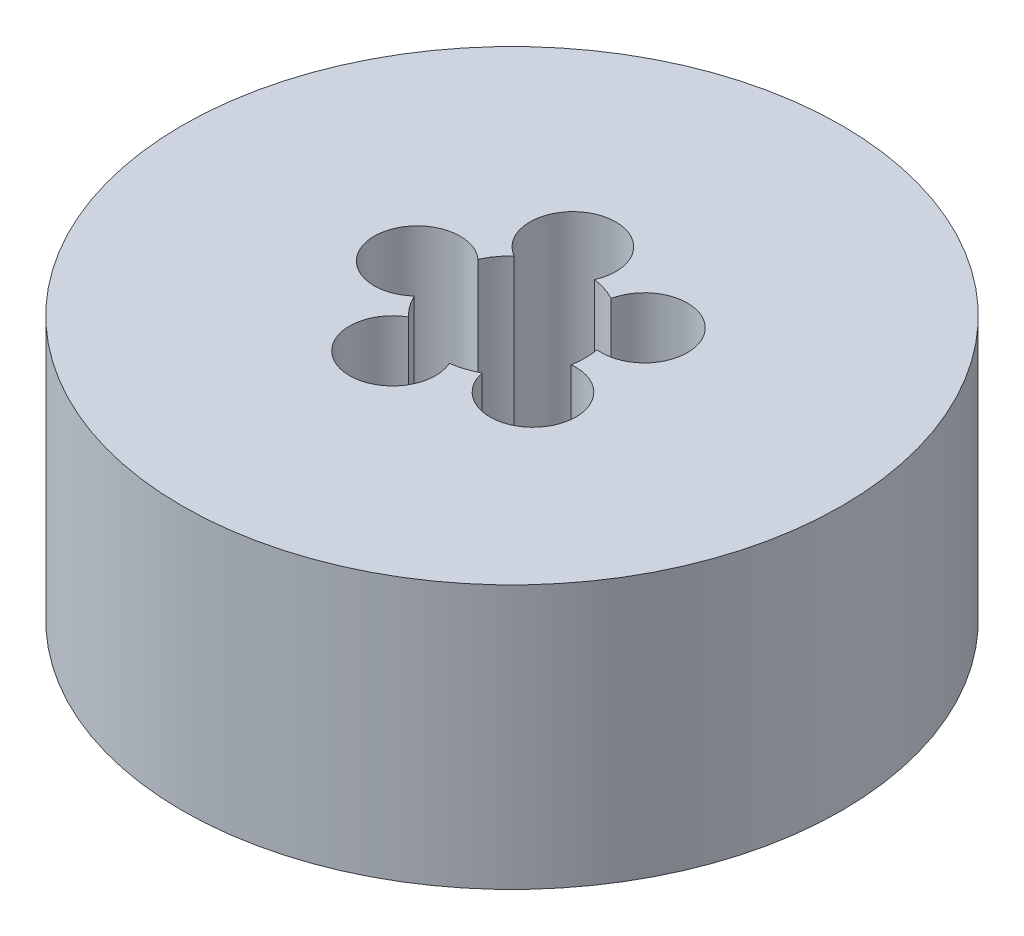
SolidWorks part; units mm, degrees
ref_plane "Front Plane" through (0, 0, 0) normal (0, 0, 1) x (1, 0, 0)
ref_plane "Top Plane" through (0, 0, 0) normal (0, 1, 0) x (1, 0, 0)
ref_plane "Right Plane" through (0, 0, 0) normal (1, 0, 0) x (0, 0, -1)
sketch "Sketch1" plane through (0, 0, 0) normal (0, 1, 0) x (1, 0, 0)
  circle A0 centre (0, 0) radius 22.5
  dimension "FLANGE_OD" = 45
extrude "Boss-Extrude1" add sketch "Sketch1" along normal blind 18
sketch "Sketch2" plane through (0, 0, 0) normal (0, 1, 0) x (1, 0, 0)
  circle A0 centre (0, 0) radius 5
  dimension "BORE_D" = 10
extrude "Cut-Extrude1" cut sketch "Sketch2" along normal through all
sketch "Sketch3" plane through (0, 18, 0) normal (0, 1, 0) x (1, 0, 0)
  circle A0 centre (0, 0) radius 6.4699 construction
  circle A1 centre (-6.4699, 0) radius 2.9363
  dimension "BOLT_D" = 5.8725
  dimension "BOLT_PCD" = 12.9399
extrude "Cut-Extrude2" cut sketch "Sketch3" against normal blind 12.5425
pattern_circular "CirPattern1" count 5 over 360 about axis through (0, 0, 0) along (0, 1, 0) of "Cut-Extrude2"
